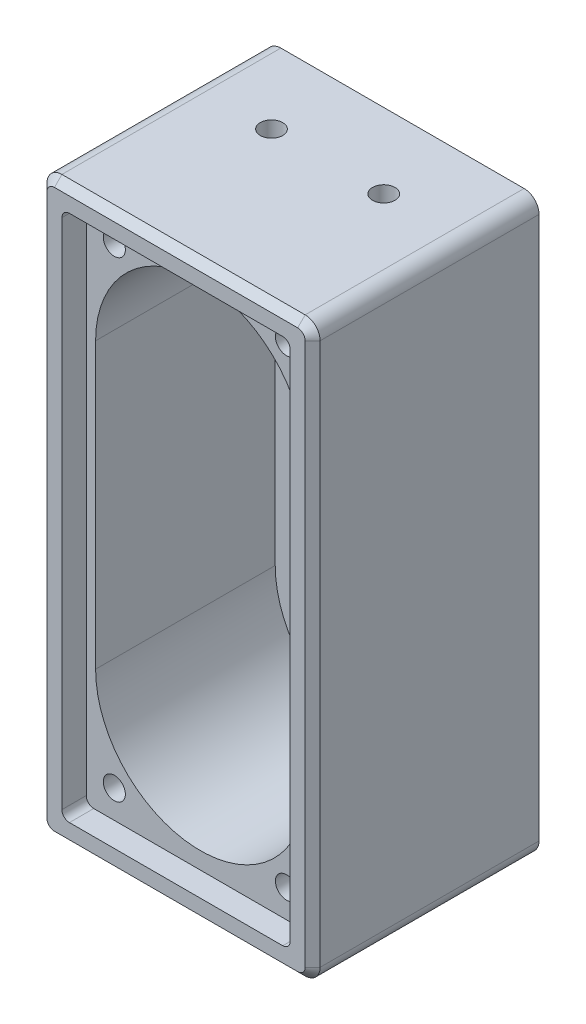
SolidWorks part; units mm, degrees
ref_plane "Front Plane" through (0, 0, 0) normal (0, 0, 1) x (1, 0, 0)
ref_plane "Top Plane" through (0, 0, 0) normal (0, 1, 0) x (1, 0, 0)
ref_plane "Right Plane" through (0, 0, 0) normal (1, 0, 0) x (0, 0, -1)
sketch "Base_Sketch" plane through (0, 0, 0) normal (0, 0, 1) x (1, 0, 0)
  line L0 (0, 23.6403) -> (0, -20.9521) construction
  line L1 (-20.2405, 0) -> (27.6726, 0) construction
  line L3 (-15.25, -35.25) -> (15.25, -35.25)
  line L4 (-15.25, -35.25) -> (-15.25, 35.25)
  line L5 (-15.25, 35.25) -> (15.25, 35.25)
  line L6 (15.25, -35.25) -> (15.25, 35.25)
  line L7 (-15.25, -35.25) -> (15.25, 35.25) construction
  line L8 (-15.25, 35.25) -> (15.25, -35.25) construction
  line L9 (-11.5, 31.5) -> (11.5, 31.5) construction
  line L10 (-11.5, 31.5) -> (-11.5, -31.5) construction
  line L11 (-11.5, -31.5) -> (11.5, -31.5) construction
  line L12 (11.5, 31.5) -> (11.5, -31.5) construction
  line L13 (-11.5, 31.5) -> (11.5, -31.5) construction
  line L14 (-11.5, -31.5) -> (11.5, 31.5) construction
  line L15 (-14, 19) -> (14, 19) construction
  line L18 (-14, 33) -> (14, 33) construction
  line L19 (-14, 33) -> (-14, -33) construction
  line L20 (-14, -33) -> (14, -33) construction
  line L21 (14, 33) -> (14, -33) construction
  line L22 (-14, 33) -> (14, -33) construction
  line L23 (-14, -33) -> (14, 33) construction
  line L24 (-14, -19) -> (14, -19) construction
  line L25 (-14, 19) -> (-14, -19)
  line L26 (14, 19) -> (14, -19)
  line L27 (-18.25, 38.25) -> (18.25, 38.25)
  line L28 (18.25, -38.25) -> (18.25, 38.25)
  line L29 (-18.25, -38.25) -> (18.25, -38.25)
  line L30 (-18.25, -38.25) -> (-18.25, 38.25)
  circle A0 centre (-11.5, 31.5) radius 1.475
  circle A1 centre (11.5, 31.5) radius 1.475
  circle A2 centre (11.5, -31.5) radius 1.475
  circle A3 centre (-11.5, -31.5) radius 1.475
  arc A6 (-14, 19) -> (14, 19) centre (0, 19) cw
  arc A7 (-14, -19) -> (14, -19) centre (0, -19) ccw
  point P1 (0, 0)
  point P11 (0, 0)
  point P19 (0, 0)
  dimension "D5" = 2.95
  dimension "D1" = 70.5
  dimension "D2" = 30.5
  dimension "D3" = 63
  dimension "D4" = 23
  dimension "D6" = 66
  dimension "D7" = 28
  dimension "D8" = 3
extrude "Boss-Extrude1" add sketch "Base_Sketch" along normal blind 3 contours L25 A7 L26 A6 | L3 L6 L5 L4 A7 L25 A6 L26 A3 A2 A1 A0 | A0 | A1 | A2 | A3 | L30 L29 L28 L27 L6 L3 L4 L5 region at (-14.4819, 0, 0) region at (0, 0, 0) region at (0, 37.4024, 0) region at (-11.5, 31.5, 0) region at (11.5, 31.5, 0) region at (11.5, -31.5, 0) region at (-11.5, -31.5, 0)
extrude "Boss-Extrude2" add sketch "Base_Sketch<8>" along normal blind 24 from surface contours L30 L29 L28 L27 L6 L3 L4 L5 | L3 L6 L5 L4 A7 L25 A6 L26 A3 A2 A1 A0 region at (-14.4819, 0, 0) region at (0, 37.4024, 0) starting at face at (0, 0, 3)
sketch "Base_Sketch<8>" plane through (0, 0, 0) normal (0, 0, 1) x (1, 0, 0) same geometry as "Base_Sketch"
extrude "Boss-Extrude3" add sketch "Base_Sketch<9>" along normal blind 3.25 from surface contours L30 L29 L28 L27 L6 L3 L4 L5 region at (0, 37.4024, 0) starting at face at (0, 0, 27)
sketch "Base_Sketch<9>" plane through (0, 0, 0) normal (0, 0, 1) x (1, 0, 0) same geometry as "Base_Sketch"
fillet "Fillet1" radius 2 4 edges at (-18.25, -38.25, 15.125) (-18.25, 38.25, 15.125) (18.25, 38.25, 15.125) (18.25, -38.25, 15.125)
fillet "Fillet2" radius 1 4 edges at (-15.25, 35.25, 28.625) (15.25, 35.25, 28.625) (15.25, -35.25, 28.625) (-15.25, -35.25, 28.625)
chamfer "Chamfer1" distance 1 angle 45 8 edges at (0, -38.25, 30.25) (-17.6642, -37.6642, 30.25) (17.6642, -37.6642, 30.25) (-18.25, 0, 30.25) (18.25, 0, 30.25) (-17.6642, 37.6642, 30.25) (17.6642, 37.6642, 30.25) (0, 38.25, 30.25)
sketch "Sketch1" plane through (0, 38.25, 0) normal (0, 1, 0) x (1, 0, 0)
  line L0 (-16.25, -10) -> (16.25, -10) construction
  line L1 (-16.25, 0) -> (-16.25, -29.25) construction
  line L2 (16.25, -29.25) -> (16.25, 0) construction
  line L3 (0, -9.6584) -> (0, -4.0925) construction
  line L4 (-16.25, 0) -> (16.25, 0) construction
  circle A0 centre (-7.5, -10) radius 1.5
  circle A1 centre (7.5, -10) radius 1.5
  point P11 (-8.8857, -8.4657)
  point P13 (0, -10)
  dimension "D1" = 3
  dimension "D2" = 10
  dimension "D3" = 7.5
extrude "Cut-Extrude1" cut sketch "Sketch1" against normal up to surface (7.4284 mm away) up to face at (0, 26, 15)
